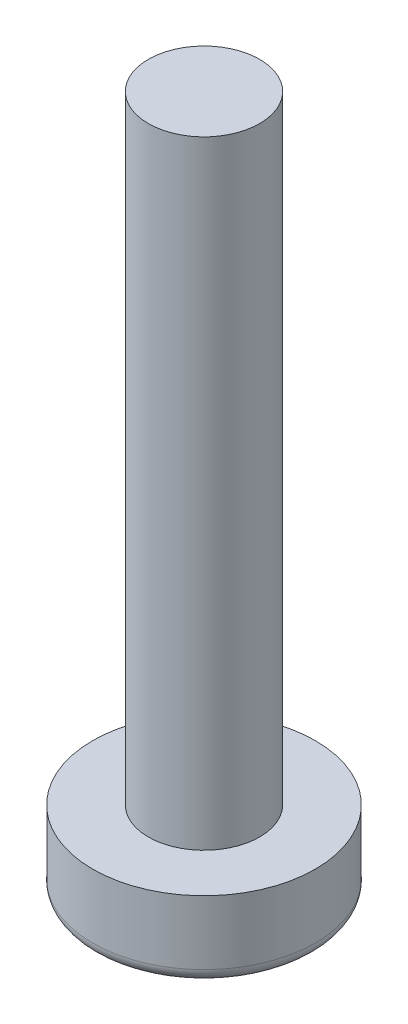
SolidWorks part; units mm, degrees
ref_plane "前视基准面" through (0, 0, 0) normal (0, 0, 1) x (1, 0, 0)
ref_plane "上视基准面" through (0, 0, 0) normal (0, 1, 0) x (1, 0, 0)
ref_plane "右视基准面" through (0, 0, 0) normal (1, 0, 0) x (0, 0, -1)
other "Configuration Table"
sketch "草图1" plane through (0, 0, 0) normal (0, 1, 0) x (1, 0, 0)
  circle A0 centre (0, 0) radius 2
  circle A1 centre (0, 0) radius 4
  dimension "D1" = 8
  dimension "D2" = 4
extrude "凸台-拉伸1" add sketch "草图1" along normal blind 2.8 contours A0 | A1 A0 region at (0, 0, 0) region at (-3.8869, 0, 0)
extrude "凸台-拉伸2" add sketch "草图1<3>" along normal blind 25 contours A0 region at (0, 0, 0)
sketch "草图1<3>" plane through (0, 0, 0) normal (0, 1, 0) x (1, 0, 0) same geometry as "草图1"
fillet "圆角1" radius 0.5 1 edges at (0, 0, 4)
